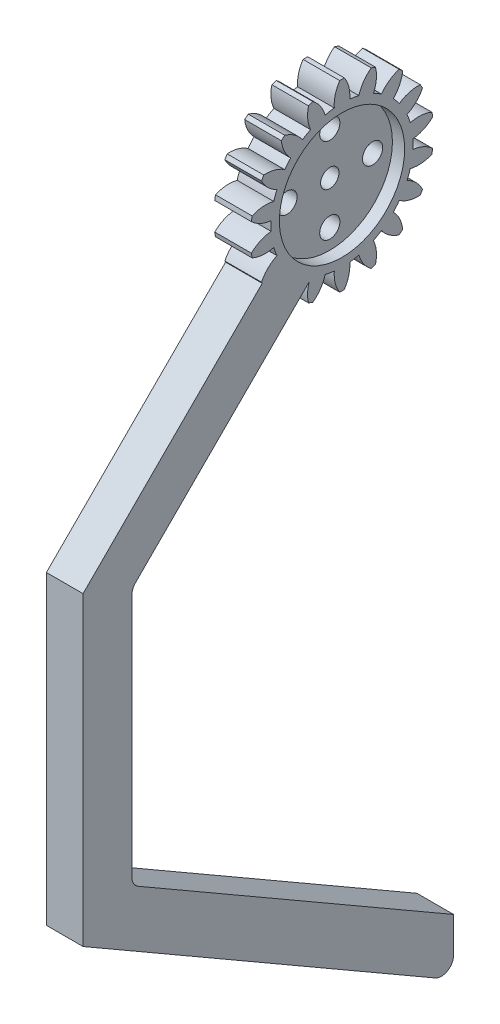
SolidWorks part; units mm, degrees
ref_plane "Plane1" through (0, 0, 0) normal (0, 0, 1) x (1, 0, 0)
ref_plane "Plane2" through (0, 0, 0) normal (0, 1, 0) x (1, 0, 0)
ref_plane "Plane3" through (0, 0, 0) normal (1, 0, 0) x (0, 0, -1)
other "Configuration Table"
sketch "HoldingSke" plane through (0, 0, 0) normal (0, 1, 0) x (1, 0, 0)
  line L0 (0, 0) -> (0.634, -0.206)
  line L1 (-15, 0) -> (100, 0) construction
  line L2 (0, 0) -> (-2.1039, 2.3779)
  line L3 (0, 0) -> (-11.863, 4.5341)
  line L4 (0, 0) -> (8.2133, 2.6687)
  line L5 (0, 0) -> (-46.8476, -17.4728)
  line L6 (0, 0) -> (-4.9738, -3.3558)
  line L7 (-2.1039, 2.3779) -> (8.6586, 51.2059)
  line L8 (-76.2, 54.61) -> (-75.7, 54.61)
  line L9 (-71.009, 38.7566) -> (-53.1078, 45.2721)
  line L10 (-76.2, 71.12) -> (104.1128, 71.12)
  line L11 (0, 0) -> (-6, 0)
  line L12 (-76.2, 101.6) -> (-76.147, 101.6)
  line L13 (24.9733, 27.94) -> (52.9518, 28.4284)
  line L14 (24.9733, 27.94) -> (24.9743, 27.94)
  line L15 (24.9733, 27.94) -> (100.4006, 29.5858)
  line L16 (-63.627, -1.5) -> (-12.827, -1.5)
  circle A0 centre (0, 0) radius 1.5
  circle A1 centre (0, 0) radius 11.624
  circle A2 centre (0, 0) radius 37.5
  circle A3 centre (0, 0) radius 1.5
  dimension "Num_teeth" = 18
  dimension "Pitch_radius" = 180.3128
  dimension "Width" = 6
  dimension "Thickness" = 6
sketch "BasProSke" plane through (0, 0, 0) normal (0, 1, 0) x (1, 0, 0)
  line L0 (-10, 0) -> (60, 0) construction
  line L1 (0, 0) -> (0, 15)
  line L2 (0, 0) -> (6, 0)
  line L3 (6, 0) -> (6, 15)
  line L4 (6, 15) -> (0, 15)
  dimension "Thickness" = 6
  dimension "Diameter" = 30
revolve "Base-Revolve" add sketch "BasProSke" angle 360 about L0
sketch "TooCutSke" plane through (0, 0, 0) normal (1, 0, 0) x (0, 0, -1)
  line L1 (0, 0) -> (0, 107) construction
  line L2 (0, 0) -> (-1.2693, 13.4402) construction
  line L3 (0, 0) -> (-4.6734, 26.504) construction
  line L4 (-1.2693, 13.4402) -> (-2.3367, 13.252) construction
  arc A0 (0.76, 11.5991) -> (-0.76, 11.5991) centre (0, 0) ccw
  arc A1 (2.2542, 14.8553) -> (-2.2542, 14.8553) centre (0, 0) ccw
  circle A2 centre (0, 0) radius 13.5 construction
  circle A3 centre (0, 0) radius 12.6859 construction
  arc A4 (-0.76, 11.5991) -> (-2.2542, 14.8553) centre (-6.1371, 11.1026) ccw
  arc A5 (2.2542, 14.8553) -> (0.76, 11.5991) centre (6.1371, 11.1026) ccw
extrude "ToothCut" cut sketch "TooCutSke" along normal through all
fillet "Breaks" [suppressed] radius 0.03 tangent propagation no
fillet "RootFillets" [suppressed] radius 0.376
pattern_circular "TeethCuts" count 18 every 20 about axis through (-10, 0, 0) along (1, 0, 0) of "ToothCut", "RootFillets", "Breaks"
sketch "HubNeaOneSke" plane through (0, 0, 0) normal (-1, 0, 0) x (0, 0, 1)
  circle A0 centre (0, 0) radius 11.624
  dimension "Diameter" = 23.248
extrude "HubNearOne" [suppressed] add sketch "HubNeaOneSke" along normal blind 44.0001
sketch "HubNeaBotSke" plane through (0, 0, 0) normal (-1, 0, 0) x (0, 0, 1)
  circle A0 centre (0, 0) radius 11.624
  dimension "Diameter" = 23.248
extrude "HubNearBoth" [suppressed] add sketch "HubNeaBotSke" along normal blind 22
ref_plane "FarPln" through (6, 0, 0) normal (1, 0, 0) x (0, 0, -1)
sketch "HubFarSke" plane through (6, 0, 0) normal (1, 0, 0) x (0, 0, -1)
  circle A0 centre (0, 0) radius 11.624
  dimension "Diameter" = 23.248
extrude "HubFar" [suppressed] add sketch "HubFarSke" along normal blind 22
sketch "BorSke" plane through (0, 0, 0) normal (1, 0, 0) x (0, 0, -1)
  circle A0 centre (0, 0) radius 1.5
extrude "Bore" cut sketch "BorSke" along normal mid plane 100.0001
sketch "KeySke" plane through (0, 0, 0) normal (1, 0, 0) x (0, 0, -1)
  line L0 (-0.6, 0) -> (-0.6, 2)
  line L1 (-0.6, 2) -> (0.6, 2)
  line L2 (0.6, 2) -> (0.6, 0)
  line L3 (0, 0) -> (0, 34) construction
  line L4 (-0.6, 0) -> (0.6, 0)
  dimension "Width" = 1.2
extrude "Keyway" [suppressed] cut sketch "KeySke" along normal mid plane 100.0001
pattern_circular "Keyway2" [suppressed] count 2 every 90 about axis through (-10, 0, 0) along (1, 0, 0)
move or copy body "右爪齿相_绕轴转半齿10度" bodies to move or copy 103 copy no rotation origin (0, 0, 0) rotation axis (-1, 0, 0) rotation angle 10
sketch "草图1" plane through (6, 0, 0) normal (1, 0, 0) x (0, 0, -1)
  line L0 (0, 0) -> (-8.2194, -8.2194) construction
  line L1 (0, 0) -> (0, -11.624) construction
  line L2 (-10.5459, -4.889) -> (-42.3657, -36.7088)
  line L3 (-10.5459, -4.889) -> (-4.889, -10.5459)
  line L4 (-42.3657, -36.7088) -> (-36.7088, -42.3657) construction
  line L5 (-4.889, -10.5459) -> (-36.7088, -42.3657) construction
  line L6 (-10.5459, -4.889) -> (-36.7088, -42.3657) construction
  line L7 (-42.3657, -36.7088) -> (-4.889, -10.5459) construction
  line L8 (-42.3657, -36.7088) -> (-42.3657, -86.7088)
  line L9 (-42.3657, -86.7088) -> (18.2561, -121.7088)
  line L10 (18.2561, -121.7088) -> (18.2561, -112.4712)
  line L11 (18.2561, -112.4712) -> (-34.3657, -82.09)
  line L12 (-34.3657, -82.09) -> (-34.3657, -40.0225)
  line L13 (-4.889, -10.5459) -> (-34.3657, -40.0225)
  circle A0 centre (0, 0) radius 11.624 construction
  arc A1 (11.5991, -0.76) -> (11.5991, 0.76) centre (0, 0) ccw construction
  arc A2 (11.5991, -0.76) -> (11.5991, 0.76) centre (0, 0) ccw construction
  point P2 (-23.6273, -23.6273)
  point P17 (-34.3657, -40.0225)
  dimension "D1" = 45
  dimension "D2" = 8
  dimension "D3" = 8
  dimension "D4" = 8
  dimension "D5" = 45
  dimension "D6" = 50
  dimension "D7" = 70
  dimension "D8" = 135
  dimension "D9" = 120
extrude "凸台-拉伸2" add sketch "草图1" against normal blind 6
sketch "草图2" plane through (6, 0, 0) normal (1, 0, 0) x (0, 0, -1)
  circle A0 centre (0, 0) radius 7 construction
  circle A1 centre (-7, 0) radius 1.65
  circle A2 centre (0, 7) radius 1.65
  circle A3 centre (7, 0) radius 1.65
  circle A4 centre (0, -7) radius 1.65
  point P14 (0, 0)
  dimension "D1" = 3.3
  dimension "D2" = 14
  dimension "D3" = 4
extrude "切除-拉伸1" cut sketch "草图2" against normal blind 6
sketch "草图3" plane through (6, 0, 0) normal (1, 0, 0) x (0, 0, -1)
  circle A0 centre (0, 0) radius 10.25
  dimension "D1" = 20.5
extrude "切除-拉伸2" cut sketch "草图3" against normal blind 2
ref_axis "夹爪啮合转轴" through (4, 0, 0) along (-1, 0, 0)
fillet "圆角1" radius 2 3 edges at (3, -82.09, 34.3657) (3, -40.0225, 34.3657) (3, -121.7088, -18.2561)
equation "' \"Module@HoldingSke\" = 6.35"
equation "' \"Num_teeth@HoldingSke\" = 12"
equation "' \"Ap@HoldingSke\" =  20"
equation "' \"Ap@HoldingSke\" = 20"
equation "' \"Width@HoldingSke\" = 0.5 * 25.4"
equation "' \"Hub_dia@HoldingSke\"= 1 * 25.4"
equation "' \"Hub_dia@HoldingSke\" = 1 * 25.4"
equation "' \"Overall_len@HoldingSke\" = 1.0 * 25.4"
equation "' \"Bore@HoldingSke\" = 0.75 * 25.4"
equation "' \"T_dim@HoldingSke\" = 0.1 * 25.4"
equation "' \"Width@KeySke\" = 0.25 * 25.4"
equation "' \"Show_teeth@HoldingSke\" = 13"
equation "' \"Backlash@HoldingSke\" = 0.009 * 25.4"
equation "' \"Addendum_fac@HoldingSke\" = 1.0"
equation "' \"Dedendum_fac@HoldingSke\" = 1.25"
equation "' \"Dedendum_add@HoldingSke\" = 0.00005 * 25.4"
equation "' \"Clearance_fac@HoldingSke\" = 0.25"
equation "\"Pitch@HoldingSke\" = 1 / \"Module@HoldingSke\""
equation "\"Overcut_dia@TooCutSke\" = (\"Num_teeth@HoldingSke\" + 2 * \"Addendum_fac@HoldingSke\") / \"Pitch@HoldingSke\" + 0.002 * 25.4"
equation "\"Pitch_dia@TooCutSke\" = \"Num_teeth@HoldingSke\" / \"Pitch@HoldingSke\""
equation "\"Base_dia@TooCutSke\" = \"Num_teeth@HoldingSke\" / \"Pitch@HoldingSke\" * cos((\"Ap@HoldingSke\"  * 3.14159265 / 180))"
equation "\"Root_dia@TooCutSke\" = (\"Num_teeth@HoldingSke\" + 2) / \"Pitch@HoldingSke\" - 2 * (\"Addendum_fac@HoldingSke\" + \"Dedendum_fac@HoldingSke\") / \"Pitch@HoldingSke\" - \"Dedendum_add@HoldingSke\" * 2"
equation "\"Half_ang@TooCutSke\" = 180 / \"Num_teeth@HoldingSke\""
equation "\"Half_CT@TooCutSke\" = \"Num_teeth@HoldingSke\" / \"Pitch@HoldingSke\" * sin((3.14159265 / 2 / \"Num_teeth@HoldingSke\")) / 2 - 7 * \"Backlash@HoldingSke\" / 4"
equation "\"Flank_rad@TooCutSke\" = \"Num_teeth@HoldingSke\" / \"Pitch@HoldingSke\" / 5"
equation "\"Radius@RootFillets\" = \"Clearance_fac@HoldingSke\" / \"Pitch@HoldingSke\" + \"Dedendum_add@HoldingSke\""
equation "\"Break_rad@Breaks\" = 0.02 / \"Pitch@HoldingSke\""
equation "\"Thickness@HoldingSke\" = \"Width@HoldingSke\""
equation "\"OAL@HoldingSke\" = \"Thickness@HoldingSke\""
equation "\"MHD@HoldingSke\" = (\"Num_teeth@HoldingSke\" + 2) / \"Pitch@HoldingSke\" - 2 * (\"Addendum_fac@HoldingSke\" + \"Dedendum_fac@HoldingSke\")  / \"Pitch@HoldingSke\" - \"Dedendum_add@HoldingSke\" * 2"
equation "\"MBD@HoldingSke\" = (\"Num_teeth@HoldingSke\" + 2) / \"Pitch@HoldingSke\" - 2 * (\"Addendum_fac@HoldingSke\" + \"Dedendum_fac@HoldingSke\")  / \"Pitch@HoldingSke\" - \"Dedendum_add@HoldingSke\" * 2 - 0.002 * 25.4"
equation "\"MHD@HoldingSke\" = ((sgn( \"MHD@HoldingSke\" - \"Hub_dia@HoldingSke\" )-1)*( \"MHD@HoldingSke\" - \"Hub_dia@HoldingSke\" ))/-2+ \"Hub_dia@HoldingSke\""
equation "\"MBD@HoldingSke\" = ((sgn( \"MBD@HoldingSke\" - \"Bore@HoldingSke\" )-1)*( \"MBD@HoldingSke\" - \"Bore@HoldingSke\" ))/-2+ \"Bore@HoldingSke\""
equation "\"OAL@HoldingSke\" = ((sgn( \"OAL@HoldingSke\" - \"Overall_len@HoldingSke\" )+1)*( \"OAL@HoldingSke\" - \"Overall_len@HoldingSke\" ))/2 + \"Overall_len@HoldingSke\" + 0.000002 * 25.4"
equation "\"Num_teeth@TeethCuts\" = int( \"Show_teeth@HoldingSke\" ) + 1"
equation "\"Num_teeth@TeethCuts\" = ((sgn( \"Num_teeth@TeethCuts\" - \"Num_teeth@HoldingSke\" )-1)*( \"Num_teeth@TeethCuts\" - \"Num_teeth@HoldingSke\" ))/-2+ \"Num_teeth@HoldingSke\""
equation "\"Num_teeth@TeethCuts\" = ((sgn( \"Num_teeth@TeethCuts\" - 2.0)+1)*( \"Num_teeth@TeethCuts\" - 2.0))/2 +2.0"
equation "\"Angle@TeethCuts\" = 360.0 / \"Num_teeth@HoldingSke\""
equation "\"Diameter@BasProSke\" = (\"Num_teeth@HoldingSke\" + 2 * \"Addendum_fac@HoldingSke\") / \"Pitch@HoldingSke\""
equation "\"Thickness@BasProSke\"  = \"Thickness@HoldingSke\""
equation "' \"Fillet_rad@BasProSke\" =  \"Thickness@HoldingSke\" * 0.05"
equation "' \"Fillet_rad@BasProSke\" = \"Thickness@HoldingSke\" * 0.05"
equation "\"MHD@HoldingSke\" = ((sgn( \"MHD@HoldingSke\" - \"Root_dia@TooCutSke\" )-1)*( \"MHD@HoldingSke\" - \"Root_dia@TooCutSke\" ))/-2+ \"Root_dia@TooCutSke\""
equation "\"Diameter@HubNeaOneSke\" = \"MHD@HoldingSke\""
equation "\"Length@HubNearOne\" = \"OAL@HoldingSke\" - \"Thickness@BasProSke\""
equation "\"Diameter@HubNeaBotSke\" = \"MHD@HoldingSke\""
equation "\"Length@HubNearBoth\" = ( \"OAL@HoldingSke\" - \"Thickness@BasProSke\" ) / 2.0"
equation "\"Thickness@FarPln\" = \"Thickness@BasProSke\""
equation "\"Diameter@HubFarSke\" = \"MHD@HoldingSke\""
equation "\"Length@HubFar\" = ( \"OAL@HoldingSke\" - \"Thickness@BasProSke\" ) / 2.0"
equation "\"Diameter@BorSke\" = \"MBD@HoldingSke\""
equation "\"D1@Bore\" = \"OAL@HoldingSke\" * 2.0"
equation "\"D1@Keyway\" = \"OAL@HoldingSke\" * 2.0"
equation "\"Offset@KeySke\" = \"T_dim@HoldingSke\" + \"MBD@HoldingSke\" / 2.0"
